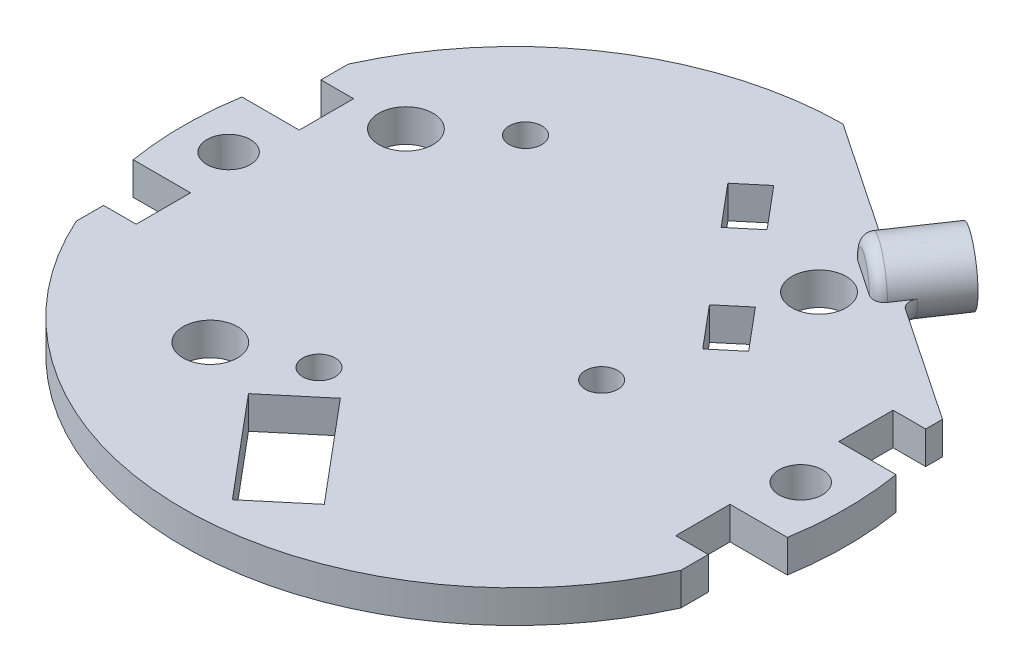
SolidWorks part; units mm, degrees
ref_plane "Alzado" through (0, 0, 0) normal (0, 0, 1) x (1, 0, 0)
ref_plane "Planta" through (0, 0, 0) normal (0, 1, 0) x (1, 0, 0)
ref_plane "Vista lateral" through (0, 0, 0) normal (1, 0, 0) x (0, 0, -1)
sketch "Croquis1" plane through (0, 0, 0) normal (0, 1, 0) x (1, 0, 0)
  circle A0 centre (0, 0) radius 30.5
extrude "Saliente-Extruir1" add sketch "Croquis1" along normal blind 3
sketch "Croquis5" plane through (0, 3, 0) normal (0, 1, 0) x (1, 0, 0)
  line L0 (0, 0) -> (0, 10)
  line L1 (28.8141, -5) -> (30.0874, -5)
  line L2 (28.8141, 5) -> (30.0874, 5)
  line L3 (-24.8141, 10) -> (-28.8141, 10)
  line L4 (24.8141, -5) -> (24.8141, -10)
  line L5 (-24.8141, -10) -> (-28.8141, -10)
  line L6 (24.8141, -5) -> (28.8141, -5)
  line L7 (24.8141, 5) -> (24.8141, 10)
  line L8 (-24.8141, 5) -> (-28.8141, 5)
  line L9 (-24.8141, 5) -> (-24.8141, 10)
  line L10 (-24.8141, -5) -> (-28.8141, -5)
  line L11 (-24.8141, -5) -> (-24.8141, -10)
  line L12 (24.8141, 5) -> (28.8141, 5)
  line L13 (24.8141, -10) -> (28.8141, -10)
  line L14 (24.8141, 10) -> (28.8141, 10)
  line L15 (-28.8141, 5) -> (-30.0874, 5)
  line L16 (-28.8141, -5) -> (-30.0874, -5)
  circle A1 centre (0, 0) radius 30.5 construction
  arc A2 (-28.8141, 10) -> (-30.0874, 5) centre (0, 0) ccw
  arc A3 (28.8141, 10) -> (28.8141, -10) centre (0, 0) cw
  arc A4 (-30.0874, -5) -> (-28.8141, -10) centre (0, 0) ccw
  arc A5 (30.0874, -5) -> (28.8141, -10) centre (0, 0) cw
  arc A6 (28.8141, 10) -> (30.0874, 5) centre (0, 0) cw
  circle M2 centre (0, 0) radius 30.5
extrude "Cortar-Extruir3" cut sketch "Croquis5" against normal blind 4 contours L11 L10 L8 L9 L3 L5 M2 | L15 L8 L9 L3 M2 | L14 L7 L12 L2 M2 | L4 L13 L1 L6 M2 region at (27.1844, 3, 7.3876) region at (27.1844, 3, -7.3876) region at (-27.1844, 3, 7.3876) region at (-27.1844, 3, -7.3876)
sketch "Croquis7" plane through (0, 3, 0) normal (0, 1, 0) x (1, 0, 0)
  line L0 (-8.1011, 29.1011) -> (9.5756, 8.0348)
  line L1 (9.5756, 8.0348) -> (27.2522, -13.0314)
  line L2 (-8.1011, 29.1011) -> (-27.2522, 13.0314)
  line L3 (27.2522, -13.0314) -> (8.1011, -29.1011)
  line L4 (8.1011, -29.1011) -> (-27.2522, 13.0314)
  line L5 (1.4284, 22.4114) -> (-0.8697, 20.4831)
  line L6 (1.4284, 22.4114) -> (4.6423, 18.5812)
  line L7 (4.6423, 18.5812) -> (2.3442, 16.6528)
  line L8 (2.3442, 16.6528) -> (-0.8697, 20.4831)
  line L9 (7.9686, 9.95) -> (11.1825, 6.1197)
  line L10 (8.1011, -29.1011) -> (5.53, -26.0369)
  line L11 (10.2667, 11.8783) -> (13.4807, 8.0481)
  line L12 (13.4807, 8.0481) -> (11.1825, 6.1197)
  line L13 (10.2667, 11.8783) -> (7.9686, 9.95)
  line L14 (5.53, -26.0369) -> (10.8923, -21.5374)
  line L15 (10.8923, -21.5374) -> (-19.3188, 14.4667)
  line L17 (-24.6811, 9.9672) -> (-19.3188, 14.4667)
  point P7 (-9.5756, -8.0348)
extrude "Cortar-Extruir5" cut sketch "Croquis7" against normal blind 4 contours L7 L6 L5 L0 | L11 L13 L0 L1 L12 region at (1.8863, 3, -19.5321) region at (10.7246, 3, -8.999)
sketch "Croquis8" plane through (0, 3, 0) normal (0, 1, 0) x (1, 0, 0)
  line L0 (-11.3137, 11.3137) -> (0, 0)
  line L2 (0, 0) -> (12, 0)
  line L3 (0, 0) -> (-11.3137, 11.3137)
  line L4 (12, 0) -> (12, 16)
  line L5 (0, 0) -> (-12, 0)
  line L6 (-12, 0) -> (-12, -16)
  line L10 (1.5586, -27.5246) -> (6.1549, -23.6679)
  line L11 (6.1549, -23.6679) -> (-1.5586, -14.4754)
  line L13 (-6.1549, -18.3321) -> (-1.5586, -14.4754)
  line L14 (1.5586, -27.5246) -> (-6.1549, -18.3321)
  circle A0 centre (0, 0) radius 30
  circle A1 centre (9, -1) radius 1.5
  circle A2 centre (-5, -13) radius 1.5
  circle A3 centre (-12, -16) radius 2.5
  circle A4 centre (-14, 15) radius 1.5
  circle A5 centre (12, 16) radius 2.5
  point P20 (-3.8567, -16.4037)
extrude "Cortar-Extruir6" cut sketch "Croquis8" against normal blind 10 contours L13 L10 L11 | A3 | L6 A3 | A3 L6 | A5 | L4 A5 | A5 L4 | L14 L10 L11 | L14 L11 | L13 L11 | A4 | L2 A1 | L2 A1 | A2 region at (10.2822, 3, -17.7178) region at (9, 3, -0.2032) region at (9, 3, 1.148) region at (-10.2822, 3, 14.2822) region at (0, 3, 21) region at (-5, 3, 13) region at (-14, 3, -15)
sketch "Croquis10" plane through (0, 3, 0) normal (0, 1, 0) x (1, 0, 0)
  line L0 (-24.8141, 10) -> (-27.8141, 10)
  line L2 (-24.8141, 10) -> (-28.8141, 10) construction
  line L4 (-27.8141, 10) -> (-27.8141, 12.5151)
  line L6 (-27.8141, 10) -> (-28.8141, 10)
  line L14 (-27.8141, -10) -> (-28.8141, -10)
  line L15 (-27.8141, -10) -> (-27.8141, -12.5151)
  line L16 (27.8141, -10) -> (27.8141, -12.5151)
  line L17 (27.8141, -10) -> (28.8141, -10)
  line L21 (27.8141, 10) -> (28.8141, 10)
  line L22 (27.8141, 10) -> (27.8141, 12.5151)
  line L23 (24.8141, 10) -> (27.8141, 10)
  circle A0 centre (-26.3141, 0) radius 2
  circle A1 centre (26.3141, 0) radius 2
  arc A2 (28.8141, 10) -> (-28.8141, 10) centre (0, 0) ccw construction
  arc A5 (-27.8141, 12.5151) -> (-28.8141, 10) centre (0, 0) ccw
  arc A7 (-27.8141, -12.5151) -> (-28.8141, -10) centre (0, 0) cw
  arc A8 (27.8141, -12.5151) -> (28.8141, -10) centre (0, 0) ccw
  arc A10 (27.8141, 12.5151) -> (28.8141, 10) centre (0, 0) cw
  line M13 (24.8141, 10) -> (28.8141, 10)
  arc M14 (28.8141, 10) -> (-28.8141, 10) centre (0, 0) ccw
  line M15 (-28.8141, 10) -> (-24.8141, 10)
  line M21 (-24.8141, -10) -> (-28.8141, -10)
  arc M22 (-28.8141, -10) -> (28.8141, -10) centre (0, 0) ccw
  line M23 (28.8141, -10) -> (24.8141, -10)
extrude "Cortar-Extruir8" cut sketch "Croquis10" against normal blind 3 contours L15 M21 M22 | L4 M15 M14 | L16 M23 M22 | L22 M13 M14 | A0 | A1 | L22 A10 L21 region at (-28.1547, 3, -10.8559) region at (28.1547, 3, -10.8559) region at (-28.1547, 3, 10.8559) region at (28.1547, 3, 10.8559) region at (-26.3141, 3, 0) region at (26.3141, 3, 0)
sketch "Croquis11" plane through (0, 3, 0) normal (0, 1, 0) x (1, 0, 0)
  line L0 (0, 0) -> (-20, 0)
  line L1 (-20, 0) -> (-20, 10)
  line L2 (0, 0) -> (0, 4.5949)
  line L3 (29.8013, 10.2046) -> (-1.7022, 31.454)
  circle A0 centre (-20, 10) radius 2.5
  circle A5 centre (0, 0) radius 31.5
  line M20 (27.8141, 10) -> (27.8141, 12.5151)
  arc M21 (27.8141, 12.5151) -> (-27.8141, 12.5151) centre (0, 0) ccw
extrude "Cortar-Extruir9" cut sketch "Croquis11" against normal blind 3 contours L3 M20 M21 | A0 region at (15.2326, 3, -22.6507) region at (-18.2822, 3, -8.2822)
sketch "Croquis13" plane through (14.0495, 0, -20.8293) normal (0.5592, 0, -0.829) x (-0.829, 0, -0.5592)
  line L1 (-16.603, 0) -> (17.2916, 0)
  line L2 (-16.603, 0) -> (-16.603, 3)
  line L3 (-16.603, 3) -> (17.2916, 3)
  line L4 (17.2916, 0) -> (17.2916, 3)
extrude "Saliente-Extruir2" add sketch "Croquis13" along normal blind 6
sketch "Croquis14" plane through (17.4047, 0, -25.8035) normal (0.5592, 0, -0.829) x (-0.829, 0, -0.5592)
  circle A0 centre (0.0043, 3) radius 3
extrude "Saliente-Extruir3" add sketch "Croquis14" against normal blind 8
sketch "Croquis17" plane through (17.4047, 0, -25.8035) normal (0.5592, 0, -0.829) x (-0.829, 0, -0.5592)
  circle A0 centre (0.0043, 3) radius 1.5
extrude "Cortar-Extruir10" cut sketch "Croquis17" against normal blind 7
sketch "Croquis19" plane through (17.4047, 0, -25.8035) normal (0.5592, 0, -0.829) x (-0.829, 0, -0.5592)
  line L0 (3.0043, 3) -> (17.2916, 3)
  line L1 (17.2916, 3) -> (17.2916, 0)
  line L2 (17.2916, 0) -> (-16.603, 0)
  line L3 (-16.603, 0) -> (-16.603, 3)
  line L4 (-16.603, 3) -> (-2.9957, 3)
  arc A0 (3.0043, 3) -> (-2.9957, 3) centre (0.0043, 3) ccw
extrude "Cortar-Extruir11" cut sketch "Croquis19" against normal blind 6
sketch "Croquis20" plane through (14.0495, 0, -20.8293) normal (0.5592, 0, -0.829) x (-0.829, 0, -0.5592)
  circle A0 centre (0.0043, 3) radius 1.5
  circle A1 centre (0.0043, 3) radius 3
extrude "Saliente-Extruir4" add sketch "Croquis20" along normal blind 5
fillet "Redondeo1" radius 1 1 edges at (12.9276, 6, -19.1736)
fillet "Redondeo2" radius 1 2 edges at (15.8046, 0.8787, -19.6455) (12.2873, 0.8787, -22.0179)
